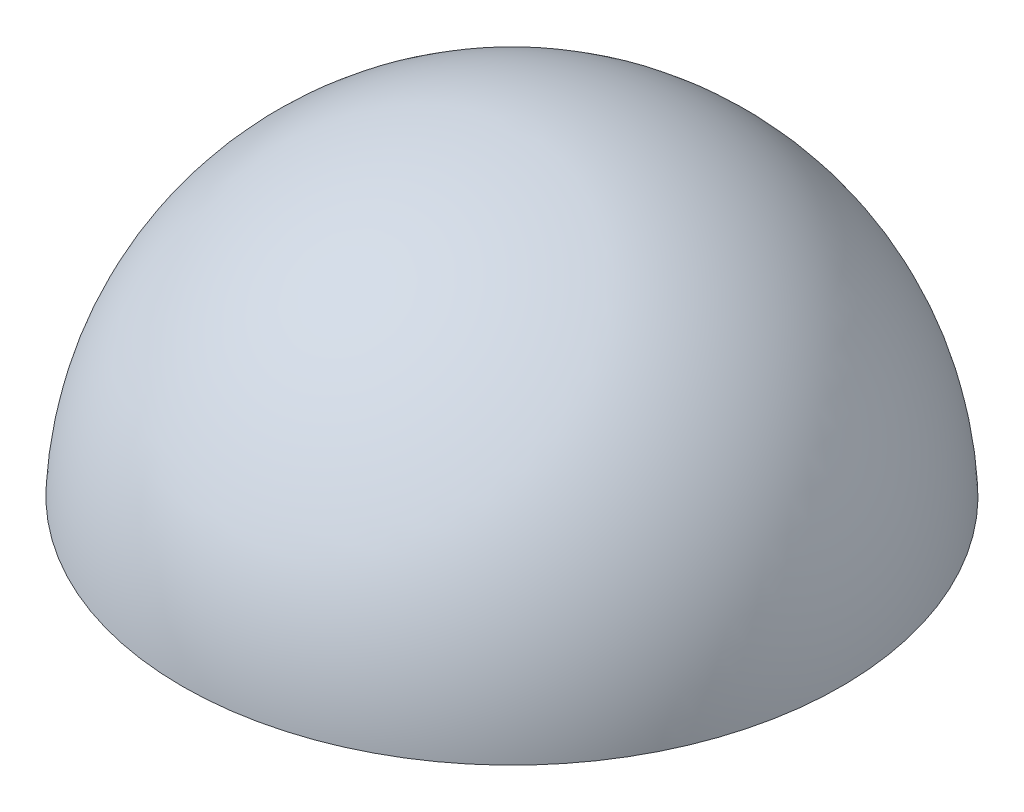
SolidWorks part; units mm, degrees
ref_plane "Front Plane" through (0, 0, 0) normal (0, 0, 1) x (1, 0, 0)
ref_plane "Top Plane" through (0, 0, 0) normal (0, 1, 0) x (1, 0, 0)
ref_plane "Right Plane" through (0, 0, 0) normal (1, 0, 0) x (0, 0, -1)
sketch "Sketch1" plane through (0, 0, 0) normal (0, 1, 0) x (1, 0, 0)
  line L0 (0, -44.45) -> (0, 44.45)
  arc A0 (0, 44.45) -> (0, -44.45) centre (0, 0) ccw
  arc A1 (0, 42.45) -> (0, -42.45) centre (0, 0) ccw
  circle A3 centre (0, 0) radius 44.45 construction
  circle A4 centre (0, 0) radius 42.45 construction
  point P1 (42.45, 0)
  point P6 (42.5077, 12.9959)
  dimension "D1" = 88.9
  dimension "D2" = 2
revolve "Revolve1" add sketch "Sketch1" angle 180 about L0 region at (-43.4561, 0, 0)
sketch "Sketch2" plane through (0, 0, 0) normal (0, 1, 0) x (1, 0, 0)
  circle A0 centre (0, 0) radius 44.45
extrude "Cut-Extrude1" cut sketch "Sketch2" along normal blind 2
sketch "30deg" plane through (0, 0, 0) normal (1, 0, 0) x (0, 0, -1)
  line L0 (0, 0) -> (38.4948, 22.225) construction
  line L1 (0, 0) -> (44.45, 0) construction
  line L7 (0, 0) -> (22.225, 38.4948) construction
  line L8 (0, 0) -> (44.45, 0) construction
  line L10 (0, 0) -> (38.4948, 22.225) construction
  line L25 (0, 0) -> (0, 49000) construction
  dimension "D2" = 3
  dimension "D3" = 30
  dimension "D1" = 44.45
sketch "Sketch4" plane through (0, 0, 0) normal (0, 1, 0) x (1, 0, 0)
  line L0 (0, 0) -> (0, 43.45)
  line L1 (0.5, 44.45) -> (-0.5, 44.45)
  line L2 (-0.5, 43.45) -> (0.5, 43.45)
  line L3 (-0.5, 43.45) -> (-0.5, 44.45)
  line L4 (0.5, 43.45) -> (0.5, 44.45)
  line L5 (0, 0) -> (21.725, 37.6288)
  line L6 (21.292, 37.8788) -> (21.792, 38.7448)
  line L7 (21.292, 37.8788) -> (22.158, 37.3788)
  line L8 (22.158, 37.3788) -> (22.658, 38.2448)
  line L9 (22.658, 38.2448) -> (21.792, 38.7448)
  line L10 (0, 0) -> (37.6288, 21.725)
  line L11 (37.3788, 22.158) -> (38.2448, 22.658)
  line L12 (37.3788, 22.158) -> (37.8788, 21.292)
  line L13 (37.8788, 21.292) -> (38.7448, 21.792)
  line L14 (38.7448, 21.792) -> (38.2448, 22.658)
  line L15 (0, 0) -> (43.45, 0)
  line L16 (43.45, 0.5) -> (44.45, 0.5)
  line L17 (43.45, 0.5) -> (43.45, -0.5)
  line L18 (43.45, -0.5) -> (44.45, -0.5)
  line L19 (44.45, -0.5) -> (44.45, 0.5)
  line L20 (0, 0) -> (37.6288, -21.725)
  line L21 (37.8788, -21.292) -> (38.7448, -21.792)
  line L22 (37.8788, -21.292) -> (37.3788, -22.158)
  line L23 (37.3788, -22.158) -> (38.2448, -22.658)
  line L24 (38.2448, -22.658) -> (38.7448, -21.792)
  line L25 (0, 0) -> (21.725, -37.6288)
  line L26 (22.158, -37.3788) -> (22.658, -38.2448)
  line L27 (22.158, -37.3788) -> (21.292, -37.8788)
  line L28 (21.292, -37.8788) -> (21.792, -38.7448)
  line L29 (21.792, -38.7448) -> (22.658, -38.2448)
  line L30 (0, 0) -> (0, -43.45)
  line L31 (0.5, -43.45) -> (0.5, -44.45)
  line L32 (0.5, -43.45) -> (-0.5, -43.45)
  line L33 (-0.5, -43.45) -> (-0.5, -44.45)
  line L34 (-0.5, -44.45) -> (0.5, -44.45)
  line L35 (0, 0) -> (-21.725, -37.6288)
  line L36 (-21.292, -37.8788) -> (-21.792, -38.7448)
  line L37 (-21.292, -37.8788) -> (-22.158, -37.3788)
  line L38 (-22.158, -37.3788) -> (-22.658, -38.2448)
  line L39 (-22.658, -38.2448) -> (-21.792, -38.7448)
  line L40 (0, 0) -> (-37.6288, -21.725)
  line L41 (-37.3788, -22.158) -> (-38.2448, -22.658)
  line L42 (-37.3788, -22.158) -> (-37.8788, -21.292)
  line L43 (-37.8788, -21.292) -> (-38.7448, -21.792)
  line L44 (-38.7448, -21.792) -> (-38.2448, -22.658)
  line L45 (0, 0) -> (-43.45, 0)
  line L46 (-43.45, -0.5) -> (-44.45, -0.5)
  line L47 (-43.45, -0.5) -> (-43.45, 0.5)
  line L48 (-43.45, 0.5) -> (-44.45, 0.5)
  line L49 (-44.45, 0.5) -> (-44.45, -0.5)
  line L50 (0, 0) -> (-37.6288, 21.725)
  line L51 (-37.8788, 21.292) -> (-38.7448, 21.792)
  line L52 (-37.8788, 21.292) -> (-37.3788, 22.158)
  line L53 (-37.3788, 22.158) -> (-38.2448, 22.658)
  line L54 (-38.2448, 22.658) -> (-38.7448, 21.792)
  line L55 (0, 0) -> (-21.725, 37.6288)
  line L56 (-22.158, 37.3788) -> (-22.658, 38.2448)
  line L57 (-22.158, 37.3788) -> (-21.292, 37.8788)
  line L58 (-21.292, 37.8788) -> (-21.792, 38.7448)
  line L59 (-21.792, 38.7448) -> (-22.658, 38.2448)
  line L60 (0, 0) -> (0, 43.45) construction
  line L61 (0, 0) -> (21.725, 37.6288) construction
  circle A0 centre (0, 0) radius 44.45 construction
  point P7 (0, 44.45)
  point P10 (0, 43.45)
  dimension "D1" = 88.9
  dimension "D2" = 1
  dimension "D3" = 1
  dimension "D5" = 30
  dimension "D4" = 12
ref_plane "Plane1" through (0, 44.45, 0) normal (0, 1, 0) x (1, 0, 0)
sketch "Sketch5" plane through (0, 44.45, 0) normal (0, 1, 0) x (1, 0, 0)
  circle A0 centre (0, 0) radius 0.5
  dimension "D1" = 1
sketch "Sketch6" plane through (0, 0, 0) normal (0, 0, 1) x (1, 0, 0)
  line L0 (44.45, 0) -> (-44.45, 0) construction
  line L1 (-43.45, 0) -> (-44.45, 0) construction
  arc A0 (-44.45, 0) -> (0, 44.45) centre (0, 0) cw
ref_axis "Axis1" through (0, 117.8347, 0) along (0, -1, 0)
sketch "Sketch7" plane through (0, 44.45, 0) normal (0, 1, 0) x (1, 0, 0)
  line L0 (0, 0) -> (0, 88.8986) construction
  line L4 (-0.5, 38.9916) -> (-0.5, 88.8986)
  line L5 (0.5, 38.9916) -> (0.5, 88.8986)
  line L7 (-0.5, 22.7195) -> (-0.5, 37.9915)
  line L9 (0.5, 22.7195) -> (0.5, 37.9915)
  line L10 (0, 0) -> (44.4493, 76.9884) construction
  line L11 (19.0628, 34.0177) -> (44.0163, 77.2384)
  line L12 (19.9288, 33.5177) -> (44.8823, 76.7384)
  line L13 (10.9267, 19.9257) -> (18.5628, 33.1516)
  line L14 (11.7928, 19.4257) -> (19.4288, 32.6516)
  line L17 (0, 0) -> (76.9884, 44.4493) construction
  line L18 (33.5177, 19.9288) -> (76.7384, 44.8823)
  line L19 (34.0177, 19.0628) -> (77.2384, 44.0163)
  line L20 (19.4257, 11.7928) -> (32.6516, 19.4288)
  line L21 (19.9257, 10.9267) -> (33.1516, 18.5628)
  line L24 (0, 0) -> (88.8986, 0) construction
  line L25 (38.9916, 0.5) -> (88.8986, 0.5)
  line L26 (38.9916, -0.5) -> (88.8986, -0.5)
  line L27 (22.7195, 0.5) -> (37.9915, 0.5)
  line L28 (22.7195, -0.5) -> (37.9915, -0.5)
  line L31 (0, 0) -> (76.9884, -44.4493) construction
  line L32 (34.0177, -19.0628) -> (77.2384, -44.0163)
  line L33 (33.5177, -19.9288) -> (76.7384, -44.8823)
  line L34 (19.9257, -10.9267) -> (33.1516, -18.5628)
  line L35 (19.4257, -11.7928) -> (32.6516, -19.4288)
  line L38 (0, 0) -> (44.4493, -76.9884) construction
  line L39 (19.9288, -33.5177) -> (44.8823, -76.7384)
  line L40 (19.0628, -34.0177) -> (44.0163, -77.2384)
  line L41 (11.7928, -19.4257) -> (19.4288, -32.6516)
  line L42 (10.9267, -19.9257) -> (18.5628, -33.1516)
  line L45 (0, 0) -> (0, -88.8986) construction
  line L46 (0.5, -38.9916) -> (0.5, -88.8986)
  line L47 (-0.5, -38.9916) -> (-0.5, -88.8986)
  line L48 (0.5, -22.7195) -> (0.5, -37.9915)
  line L49 (-0.5, -22.7195) -> (-0.5, -37.9915)
  line L52 (0, 0) -> (-44.4493, -76.9884) construction
  line L53 (-19.0628, -34.0177) -> (-44.0163, -77.2384)
  line L54 (-19.9288, -33.5177) -> (-44.8823, -76.7384)
  line L55 (-10.9267, -19.9257) -> (-18.5628, -33.1516)
  line L56 (-11.7928, -19.4257) -> (-19.4288, -32.6516)
  line L59 (0, 0) -> (-76.9884, -44.4493) construction
  line L60 (-33.5177, -19.9288) -> (-76.7384, -44.8823)
  line L61 (-34.0177, -19.0628) -> (-77.2384, -44.0163)
  line L62 (-19.4257, -11.7928) -> (-32.6516, -19.4288)
  line L63 (-19.9257, -10.9267) -> (-33.1516, -18.5628)
  line L66 (0, 0) -> (-88.8986, 0) construction
  line L67 (-38.9916, -0.5) -> (-88.8986, -0.5)
  line L68 (-38.9916, 0.5) -> (-88.8986, 0.5)
  line L69 (-22.7195, -0.5) -> (-37.9915, -0.5)
  line L70 (-22.7195, 0.5) -> (-37.9915, 0.5)
  line L73 (0, 0) -> (-76.9884, 44.4493) construction
  line L74 (-34.0177, 19.0628) -> (-77.2384, 44.0163)
  line L75 (-33.5177, 19.9288) -> (-76.7384, 44.8823)
  line L76 (-19.9257, 10.9267) -> (-33.1516, 18.5628)
  line L77 (-19.4257, 11.7928) -> (-32.6516, 19.4288)
  line L80 (0, 0) -> (-44.4493, 76.9884) construction
  line L81 (-19.9288, 33.5177) -> (-44.8823, 76.7384)
  line L82 (-19.0628, 34.0177) -> (-44.0163, 77.2384)
  line L83 (-11.7928, 19.4257) -> (-19.4288, 32.6516)
  line L84 (-10.9267, 19.9257) -> (-18.5628, 33.1516)
  line L87 (0, 0) -> (0.5, 0) construction
  line L89 (-0.5, 1.866) -> (-0.5, 21.7192)
  line L90 (-0.5, 1.866) -> (-10.4266, 19.0594)
  line L91 (0.5, 1.866) -> (10.4266, 19.0594)
  line L92 (0.5, 1.866) -> (0.5, 21.7192)
  line L93 (1.366, 1.366) -> (18.5594, 11.2926)
  line L94 (1.366, 1.366) -> (11.2926, 18.5594)
  line L95 (1.866, 0.5) -> (21.7192, 0.5)
  line L96 (1.866, 0.5) -> (19.0594, 10.4266)
  line L97 (1.866, -0.5) -> (19.0594, -10.4266)
  line L98 (1.866, -0.5) -> (21.7192, -0.5)
  line L99 (1.366, -1.366) -> (11.2926, -18.5594)
  line L100 (1.366, -1.366) -> (18.5594, -11.2926)
  line L101 (0.5, -1.866) -> (0.5, -21.7192)
  line L102 (0.5, -1.866) -> (10.4266, -19.0594)
  line L103 (-0.5, -1.866) -> (-10.4266, -19.0594)
  line L104 (-0.5, -1.866) -> (-0.5, -21.7192)
  line L105 (-1.366, -1.366) -> (-11.2926, -18.5594)
  line L106 (-1.366, -1.366) -> (-18.5594, -11.2926)
  line L107 (-1.866, -0.5) -> (-21.7192, -0.5)
  line L108 (-1.866, -0.5) -> (-19.0594, -10.4266)
  line L109 (-1.866, 0.5) -> (-19.0594, 10.4266)
  line L110 (-1.866, 0.5) -> (-21.7192, 0.5)
  line L111 (-1.366, 1.366) -> (-11.2926, 18.5594)
  line L112 (-1.366, 1.366) -> (-18.5594, 11.2926)
  circle A0 centre (0, 0) radius 22.225 construction
  circle A1 centre (0, 0) radius 38.4948 construction
  arc A2 (-0.5, 38.9916) -> (-19.0628, 34.0177) centre (0, 0) ccw
  arc A3 (-0.5, 22.7195) -> (-10.9267, 19.9257) centre (0, 0) ccw
  arc A4 (-0.5, 37.9915) -> (-18.5628, 33.1516) centre (0, 0) ccw
  arc A5 (-0.5, 21.7192) -> (-10.4266, 19.0594) centre (0, 0) ccw
  arc A6 (0.5, 88.8986) -> (-0.5, 88.8986) centre (0, 0) ccw
  circle A9 centre (0, 0) radius 88.9 construction
  circle A10 centre (0, 0) radius 38.9948 construction
  circle A11 centre (0, 0) radius 37.9948 construction
  circle A13 centre (0, 0) radius 21.725 construction
  circle A14 centre (0, 0) radius 22.725 construction
  arc A15 (44.8823, 76.7384) -> (44.0163, 77.2384) centre (0, 0) ccw
  arc A16 (77.2384, 44.0163) -> (76.7384, 44.8823) centre (0, 0) ccw
  arc A17 (88.8986, -0.5) -> (88.8986, 0.5) centre (0, 0) ccw
  arc A18 (76.7384, -44.8823) -> (77.2384, -44.0163) centre (0, 0) ccw
  arc A19 (44.0163, -77.2384) -> (44.8823, -76.7384) centre (0, 0) ccw
  arc A20 (-0.5, -88.8986) -> (0.5, -88.8986) centre (0, 0) ccw
  arc A21 (-44.8823, -76.7384) -> (-44.0163, -77.2384) centre (0, 0) ccw
  arc A22 (-77.2384, -44.0163) -> (-76.7384, -44.8823) centre (0, 0) ccw
  arc A23 (-88.8986, 0.5) -> (-88.8986, -0.5) centre (0, 0) ccw
  arc A24 (-76.7384, 44.8823) -> (-77.2384, 44.0163) centre (0, 0) ccw
  arc A25 (-44.0163, 77.2384) -> (-44.8823, 76.7384) centre (0, 0) ccw
  arc A26 (-34.0177, 19.0628) -> (-38.9916, 0.5) centre (0, 0) ccw
  arc A27 (-33.1516, 18.5628) -> (-37.9915, 0.5) centre (0, 0) ccw
  arc A28 (-19.9288, 33.5177) -> (-33.5177, 19.9288) centre (0, 0) ccw
  arc A29 (-19.4288, 32.6516) -> (-32.6516, 19.4288) centre (0, 0) ccw
  arc A30 (19.0628, 34.0177) -> (0.5, 38.9916) centre (0, 0) ccw
  arc A31 (18.5628, 33.1516) -> (0.5, 37.9915) centre (0, 0) ccw
  arc A32 (32.6516, 19.4288) -> (19.4288, 32.6516) centre (0, 0) ccw
  arc A33 (33.5177, 19.9288) -> (19.9288, 33.5177) centre (0, 0) ccw
  arc A34 (37.9915, 0.5) -> (33.1516, 18.5628) centre (0, 0) ccw
  arc A35 (38.9916, 0.5) -> (34.0177, 19.0628) centre (0, 0) ccw
  arc A36 (33.1516, -18.5628) -> (37.9915, -0.5) centre (0, 0) ccw
  arc A37 (34.0177, -19.0628) -> (38.9916, -0.5) centre (0, 0) ccw
  arc A38 (19.4288, -32.6516) -> (32.6516, -19.4288) centre (0, 0) ccw
  arc A39 (19.9288, -33.5177) -> (33.5177, -19.9288) centre (0, 0) ccw
  arc A40 (0.5, -37.9915) -> (18.5628, -33.1516) centre (0, 0) ccw
  arc A41 (0.5, -38.9916) -> (19.0628, -34.0177) centre (0, 0) ccw
  arc A42 (-18.5628, -33.1516) -> (-0.5, -37.9915) centre (0, 0) ccw
  arc A43 (-19.0628, -34.0177) -> (-0.5, -38.9916) centre (0, 0) ccw
  arc A44 (-33.5177, -19.9288) -> (-19.9288, -33.5177) centre (0, 0) ccw
  arc A45 (-32.6516, -19.4288) -> (-19.4288, -32.6516) centre (0, 0) ccw
  arc A46 (-38.9916, -0.5) -> (-34.0177, -19.0628) centre (0, 0) ccw
  arc A47 (-37.9915, -0.5) -> (-33.1516, -18.5628) centre (0, 0) ccw
  arc A48 (-11.7928, 19.4257) -> (-19.4257, 11.7928) centre (0, 0) ccw
  arc A49 (-11.2926, 18.5594) -> (-18.5594, 11.2926) centre (0, 0) ccw
  arc A50 (-19.9257, 10.9267) -> (-22.7195, 0.5) centre (0, 0) ccw
  arc A51 (-19.0594, 10.4266) -> (-21.7192, 0.5) centre (0, 0) ccw
  arc A52 (-21.7192, -0.5) -> (-19.0594, -10.4266) centre (0, 0) ccw
  arc A53 (-22.7195, -0.5) -> (-19.9257, -10.9267) centre (0, 0) ccw
  arc A54 (10.4266, 19.0594) -> (0.5, 21.7192) centre (0, 0) ccw
  arc A55 (10.9267, 19.9257) -> (0.5, 22.7195) centre (0, 0) ccw
  arc A56 (18.5594, 11.2926) -> (11.2926, 18.5594) centre (0, 0) ccw
  arc A57 (19.4257, 11.7928) -> (11.7928, 19.4257) centre (0, 0) ccw
  arc A58 (21.7192, 0.5) -> (19.0594, 10.4266) centre (0, 0) ccw
  arc A59 (22.7195, 0.5) -> (19.9257, 10.9267) centre (0, 0) ccw
  arc A60 (19.9257, -10.9267) -> (22.7195, -0.5) centre (0, 0) ccw
  arc A61 (19.0594, -10.4266) -> (21.7192, -0.5) centre (0, 0) ccw
  arc A62 (11.2926, -18.5594) -> (18.5594, -11.2926) centre (0, 0) ccw
  arc A63 (11.7928, -19.4257) -> (19.4257, -11.7928) centre (0, 0) ccw
  arc A64 (0.5, -22.7195) -> (10.9267, -19.9257) centre (0, 0) ccw
  arc A65 (0.5, -21.7192) -> (10.4266, -19.0594) centre (0, 0) ccw
  arc A66 (-10.4266, -19.0594) -> (-0.5, -21.7192) centre (0, 0) ccw
  arc A67 (-10.9267, -19.9257) -> (-0.5, -22.7195) centre (0, 0) ccw
  arc A68 (-19.4257, -11.7928) -> (-11.7928, -19.4257) centre (0, 0) ccw
  arc A69 (-18.5594, -11.2926) -> (-11.2926, -18.5594) centre (0, 0) ccw
  point P11 (21.725, 0)
  point P13 (22.725, 0)
  point P17 (0.5, 0)
  point P19 (-0.5, 0)
  point P27 (38.9948, 0)
  point P30 (37.9948, 0)
  point P114 (-1.366, 1.366)
  dimension "D5" = 177.8
  dimension "D1" = 0.5
  dimension "D2" = 0.5
  dimension "D6" = 12
sketch "Sketch9" plane through (0, 44.45, 0) normal (0, 1, 0) x (1, 0, 0)
  line L0 (0, 0) -> (0, -88.9)
  circle A0 centre (0, 0) radius 22.225
  circle A1 centre (0, 0) radius 38.4948
  circle A2 centre (0, 0) radius 88.9
  circle A3 centre (0, 0) radius 38.4948 construction
  circle A4 centre (0, 0) radius 22.225 construction
  dimension "D1" = 177.8
sketch "Sketch10" plane through (0, 44.45, 0) normal (0, 1, 0) x (1, 0, 0)
  line L0 (88.9, 0) -> (-88.9, 0) construction
  line L1 (0, 88.9) -> (0, -88.9) construction
  line L2 (-29.64, 88.9) -> (-29.64, -88.9) construction
  line L3 (-59.28, 88.9) -> (-59.28, -88.9) construction
  line L4 (-88.92, 88.9) -> (-88.92, -88.9) construction
  line L5 (29.64, 88.9) -> (29.64, -88.9) construction
  line L6 (59.28, 88.9) -> (59.28, -88.9) construction
  line L7 (88.92, 88.9) -> (88.92, -88.9) construction
  line L8 (-89.42, 88.9) -> (-89.42, -88.9)
  line L9 (-59.78, 88.9) -> (-59.78, 0.5)
  line L10 (-30.14, 88.9) -> (-30.14, 0.5)
  line L11 (-0.5, 88.9) -> (-0.5, 0.5)
  line L12 (29.14, 88.9) -> (29.14, 0.5)
  line L13 (58.78, 88.9) -> (58.78, 0.5)
  line L14 (88.42, 88.9) -> (88.42, 0.5)
  line L15 (-88.42, 88.9) -> (-88.42, 0.5)
  line L16 (-58.78, 88.9) -> (-58.78, 0.5)
  line L17 (-29.14, 88.9) -> (-29.14, 0.5)
  line L18 (0.5, 88.9) -> (0.5, 0.5)
  line L19 (30.14, 88.9) -> (30.14, 0.5)
  line L20 (59.78, 88.9) -> (59.78, 0.5)
  line L21 (89.42, 88.9) -> (89.42, -88.9)
  line L22 (88.42, 0.5) -> (59.78, 0.5)
  line L23 (88.42, -0.5) -> (59.78, -0.5)
  line L24 (-88.42, -0.5) -> (-88.42, -88.9)
  line L25 (88.9, 0.5) -> (-88.9, 0.5) construction
  line L26 (88.9, -0.5) -> (-88.9, -0.5) construction
  line L27 (-59.78, 0.5) -> (-88.42, 0.5)
  line L28 (-88.42, 88.9) -> (-88.42, -88.9) construction
  line L29 (-59.78, -0.5) -> (-88.42, -0.5)
  line L30 (-59.78, -0.5) -> (-59.78, -88.9)
  line L31 (-58.78, -0.5) -> (-58.78, -88.9)
  line L32 (-59.78, 88.9) -> (-59.78, -88.9) construction
  line L33 (-30.14, -0.5) -> (-30.14, -88.9)
  line L34 (-58.78, 88.9) -> (-58.78, -88.9) construction
  line L35 (-30.14, 88.9) -> (-30.14, -88.9) construction
  line L36 (-29.14, -0.5) -> (-29.14, -88.9)
  line L37 (-29.14, 88.9) -> (-29.14, -88.9) construction
  line L38 (-0.5, -0.5) -> (-0.5, -88.9)
  line L39 (-0.5, 88.9) -> (-0.5, -88.9) construction
  line L40 (0.5, -0.5) -> (0.5, -88.9)
  line L41 (0.5, 88.9) -> (0.5, -88.9) construction
  line L42 (29.14, -0.5) -> (29.14, -88.9)
  line L43 (29.14, 88.9) -> (29.14, -88.9) construction
  line L44 (30.14, -0.5) -> (30.14, -88.9)
  line L45 (30.14, 88.9) -> (30.14, -88.9) construction
  line L46 (58.78, -0.5) -> (58.78, -88.9)
  line L47 (58.78, 88.9) -> (58.78, -88.9) construction
  line L48 (59.78, -0.5) -> (59.78, -88.9)
  line L49 (59.78, 88.9) -> (59.78, -88.9) construction
  line L50 (88.42, -0.5) -> (88.42, -88.9)
  line L51 (88.42, 88.9) -> (88.42, -88.9) construction
  line L52 (58.78, 0.5) -> (30.14, 0.5)
  line L53 (58.78, -0.5) -> (30.14, -0.5)
  line L54 (-30.14, 0.5) -> (-58.78, 0.5)
  line L55 (-30.14, -0.5) -> (-58.78, -0.5)
  line L56 (-0.5, 0.5) -> (-29.14, 0.5)
  line L57 (-0.5, -0.5) -> (-29.14, -0.5)
  line L58 (29.14, 0.5) -> (0.5, 0.5)
  line L59 (29.14, -0.5) -> (0.5, -0.5)
  arc A0 (-89.42, 88.9) -> (-88.42, 88.9) centre (-88.92, 88.9) cw
  arc A1 (-89.42, -88.9) -> (-88.42, -88.9) centre (-88.92, -88.9) ccw
  arc A2 (-59.78, 88.9) -> (-58.78, 88.9) centre (-59.28, 88.9) cw
  arc A3 (-59.78, -88.9) -> (-58.78, -88.9) centre (-59.28, -88.9) ccw
  arc A4 (-30.14, 88.9) -> (-29.14, 88.9) centre (-29.64, 88.9) cw
  arc A5 (-30.14, -88.9) -> (-29.14, -88.9) centre (-29.64, -88.9) ccw
  arc A6 (-0.5, 88.9) -> (0.5, 88.9) centre (0, 88.9) cw
  arc A7 (-0.5, -88.9) -> (0.5, -88.9) centre (0, -88.9) ccw
  arc A8 (29.14, 88.9) -> (30.14, 88.9) centre (29.64, 88.9) cw
  arc A9 (29.14, -88.9) -> (30.14, -88.9) centre (29.64, -88.9) ccw
  arc A10 (58.78, 88.9) -> (59.78, 88.9) centre (59.28, 88.9) cw
  arc A11 (58.78, -88.9) -> (59.78, -88.9) centre (59.28, -88.9) ccw
  arc A12 (88.42, 88.9) -> (89.42, 88.9) centre (88.92, 88.9) cw
  arc A13 (88.42, -88.9) -> (89.42, -88.9) centre (88.92, -88.9) ccw
  arc A15 (-88.9, 0.5) -> (-88.92, 0.4996) centre (-88.9, 0) ccw
  arc A16 (-88.92, -0.4996) -> (-88.9, -0.5) centre (-88.9, 0) ccw
  point P4 (0, 0)
  point P8 (0, 0)
  dimension "D1" = 177.8
  dimension "D3" = 0.5
  dimension "D4" = 0.5
  dimension "D5" = 0.5
  dimension "D6" = 0.5
  dimension "D2" = 4
sketch "Sketch13" plane through (0, 44.45, 0) normal (0, 1, 0) x (1, 0, 0)
  line L0 (0, -11.5265) -> (0, 11.5265) construction
  line L1 (-11.5265, 0) -> (11.5265, 0) construction
  line L2 (-11.5265, -0.5) -> (-0.5, -0.5)
  line L3 (-18.1069, 3.2902) -> (-11.5265, 3.2902) construction
  line L4 (-18.1069, 3.2902) -> (-18.1069, -3.2902) construction
  line L5 (-18.1069, -3.2902) -> (-11.5265, -3.2902) construction
  line L6 (-11.5265, 3.2902) -> (-11.5265, -3.2902) construction
  line L7 (-3.2902, 18.1069) -> (3.2902, 18.1069) construction
  line L8 (-3.2902, 18.1069) -> (-3.2902, 11.5265) construction
  line L9 (-3.2902, 11.5265) -> (3.2902, 11.5265) construction
  line L10 (3.2902, 18.1069) -> (3.2902, 11.5265) construction
  line L11 (0.5, -11.5265) -> (0.5, -0.5)
  line L12 (-11.5265, 0.5) -> (-0.5, 0.5)
  line L13 (-0.5, -11.5265) -> (-0.5, -0.5)
  line L14 (-0.5, 0.5) -> (-0.5, 11.5265)
  line L15 (0.5, 0.5) -> (0.5, 11.5265)
  line L16 (-0.5, -11.5265) -> (-0.5, 11.5265) construction
  line L17 (0.5, 0.5) -> (11.5265, 0.5)
  line L18 (0.5, -11.5265) -> (0.5, 11.5265) construction
  line L19 (0.5, -0.5) -> (11.5265, -0.5)
  line L20 (-11.5265, 0.5) -> (11.5265, 0.5) construction
  line L21 (-11.5265, 0.5) -> (-11.5265, -0.5)
  line L22 (-11.5265, -0.5) -> (11.5265, -0.5) construction
  line L23 (11.5265, 0.5) -> (11.5265, -0.5)
  line L24 (-0.5, -11.5265) -> (0.5, -11.5265)
  line L25 (-0.5, 11.5265) -> (0.5, 11.5265)
  line L26 (18.1035, -0.5) -> (29.13, -0.5)
  line L27 (30.13, -11.5265) -> (30.13, -0.5)
  line L28 (18.1035, 0.5) -> (29.13, 0.5)
  line L29 (29.13, -11.5265) -> (29.13, -0.5)
  line L30 (29.13, 0.5) -> (29.13, 11.5265)
  line L31 (30.13, 0.5) -> (30.13, 11.5265)
  line L32 (30.13, 0.5) -> (41.1565, 0.5)
  line L33 (30.13, -0.5) -> (41.1565, -0.5)
  line L34 (18.1035, 0.5) -> (18.1035, -0.5)
  line L35 (41.1565, 0.5) -> (41.1565, -0.5)
  line L36 (29.13, -11.5265) -> (30.13, -11.5265)
  line L37 (29.13, 11.5265) -> (30.13, 11.5265)
  line L38 (29.63, -11.5265) -> (29.63, 11.5265) construction
  line L39 (18.1035, 0) -> (41.1565, 0) construction
  line L40 (11.5231, 3.2902) -> (18.1035, 3.2902) construction
  line L41 (11.5231, 3.2902) -> (11.5231, -3.2902) construction
  line L42 (11.5231, -3.2902) -> (18.1035, -3.2902) construction
  line L43 (18.1035, 3.2902) -> (18.1035, -3.2902) construction
  line L44 (26.3398, 18.1069) -> (32.9202, 18.1069) construction
  line L45 (26.3398, 18.1069) -> (26.3398, 11.5265) construction
  line L46 (26.3398, 11.5265) -> (32.9202, 11.5265) construction
  line L47 (32.9202, 18.1069) -> (32.9202, 11.5265) construction
  line L48 (47.7335, -0.5) -> (58.76, -0.5)
  line L49 (59.76, -11.5265) -> (59.76, -0.5)
  line L50 (47.7335, 0.5) -> (58.76, 0.5)
  line L51 (58.76, -11.5265) -> (58.76, -0.5)
  line L52 (58.76, 0.5) -> (58.76, 11.5265)
  line L53 (59.76, 0.5) -> (59.76, 11.5265)
  line L54 (59.76, 0.5) -> (70.7865, 0.5)
  line L55 (59.76, -0.5) -> (70.7865, -0.5)
  line L56 (47.7335, 0.5) -> (47.7335, -0.5)
  line L57 (70.7865, 0.5) -> (70.7865, -0.5)
  line L58 (58.76, -11.5265) -> (59.76, -11.5265)
  line L59 (58.76, 11.5265) -> (59.76, 11.5265)
  line L60 (59.26, -11.5265) -> (59.26, 11.5265) construction
  line L61 (47.7335, 0) -> (70.7865, 0) construction
  line L62 (41.1531, 3.2902) -> (47.7335, 3.2902) construction
  line L63 (41.1531, 3.2902) -> (41.1531, -3.2902) construction
  line L64 (41.1531, -3.2902) -> (47.7335, -3.2902) construction
  line L65 (47.7335, 3.2902) -> (47.7335, -3.2902) construction
  line L66 (55.9698, 18.1069) -> (62.5502, 18.1069) construction
  line L67 (55.9698, 18.1069) -> (55.9698, 11.5265) construction
  line L68 (55.9698, 11.5265) -> (62.5502, 11.5265) construction
  line L69 (62.5502, 18.1069) -> (62.5502, 11.5265) construction
  line L70 (-11.5265, 29.13) -> (-0.5, 29.13)
  line L71 (0.5, 18.1035) -> (0.5, 29.13)
  line L72 (-11.5265, 30.13) -> (-0.5, 30.13)
  line L73 (-0.5, 18.1035) -> (-0.5, 29.13)
  line L74 (-0.5, 30.13) -> (-0.5, 41.1565)
  line L75 (0.5, 30.13) -> (0.5, 41.1565)
  line L76 (0.5, 30.13) -> (11.5265, 30.13)
  line L77 (0.5, 29.13) -> (11.5265, 29.13)
  line L78 (-11.5265, 30.13) -> (-11.5265, 29.13)
  line L79 (11.5265, 30.13) -> (11.5265, 29.13)
  line L80 (-0.5, 18.1035) -> (0.5, 18.1035)
  line L81 (-0.5, 41.1565) -> (0.5, 41.1565)
  line L82 (18.1035, 29.13) -> (29.13, 29.13)
  line L83 (30.13, 18.1035) -> (30.13, 29.13)
  line L84 (18.1035, 30.13) -> (29.13, 30.13)
  line L85 (29.13, 18.1035) -> (29.13, 29.13)
  line L86 (29.13, 30.13) -> (29.13, 41.1565)
  line L87 (30.13, 30.13) -> (30.13, 41.1565)
  line L88 (30.13, 30.13) -> (41.1565, 30.13)
  line L89 (30.13, 29.13) -> (41.1565, 29.13)
  line L90 (18.1035, 30.13) -> (18.1035, 29.13)
  line L91 (41.1565, 30.13) -> (41.1565, 29.13)
  line L92 (29.13, 18.1035) -> (30.13, 18.1035)
  line L93 (29.13, 41.1565) -> (30.13, 41.1565)
  line L94 (47.7335, 29.13) -> (58.76, 29.13)
  line L95 (59.76, 18.1035) -> (59.76, 29.13)
  line L96 (47.7335, 30.13) -> (58.76, 30.13)
  line L97 (58.76, 18.1035) -> (58.76, 29.13)
  line L98 (58.76, 30.13) -> (58.76, 41.1565)
  line L99 (59.76, 30.13) -> (59.76, 41.1565)
  line L100 (59.76, 30.13) -> (70.7865, 30.13)
  line L101 (59.76, 29.13) -> (70.7865, 29.13)
  line L102 (47.7335, 30.13) -> (47.7335, 29.13)
  line L103 (70.7865, 30.13) -> (70.7865, 29.13)
  line L104 (58.76, 18.1035) -> (59.76, 18.1035)
  line L105 (58.76, 41.1565) -> (59.76, 41.1565)
  line L106 (0, 18.1035) -> (0, 41.1565) construction
  line L107 (-11.5265, 29.63) -> (11.5265, 29.63) construction
  line L108 (-18.1069, 32.9202) -> (-11.5265, 32.9202) construction
  line L109 (-18.1069, 32.9202) -> (-18.1069, 26.3398) construction
  line L110 (-18.1069, 26.3398) -> (-11.5265, 26.3398) construction
  line L111 (-11.5265, 32.9202) -> (-11.5265, 26.3398) construction
  line L112 (-3.2902, 47.7369) -> (3.2902, 47.7369) construction
  line L113 (-3.2902, 47.7369) -> (-3.2902, 41.1565) construction
  line L114 (-3.2902, 41.1565) -> (3.2902, 41.1565) construction
  line L115 (3.2902, 47.7369) -> (3.2902, 41.1565) construction
  line L116 (29.63, 18.1035) -> (29.63, 41.1565) construction
  line L117 (18.1035, 29.63) -> (41.1565, 29.63) construction
  line L118 (11.5231, 32.9202) -> (18.1035, 32.9202) construction
  line L119 (11.5231, 32.9202) -> (11.5231, 26.3398) construction
  line L120 (11.5231, 26.3398) -> (18.1035, 26.3398) construction
  line L121 (18.1035, 32.9202) -> (18.1035, 26.3398) construction
  line L122 (26.3398, 47.7369) -> (32.9202, 47.7369) construction
  line L123 (26.3398, 47.7369) -> (26.3398, 41.1565) construction
  line L124 (26.3398, 41.1565) -> (32.9202, 41.1565) construction
  line L125 (32.9202, 47.7369) -> (32.9202, 41.1565) construction
  line L126 (59.26, 18.1035) -> (59.26, 41.1565) construction
  line L127 (47.7335, 29.63) -> (70.7865, 29.63) construction
  line L128 (41.1531, 32.9202) -> (47.7335, 32.9202) construction
  line L129 (41.1531, 32.9202) -> (41.1531, 26.3398) construction
  line L130 (41.1531, 26.3398) -> (47.7335, 26.3398) construction
  line L131 (47.7335, 32.9202) -> (47.7335, 26.3398) construction
  line L132 (55.9698, 47.7369) -> (62.5502, 47.7369) construction
  line L133 (55.9698, 47.7369) -> (55.9698, 41.1565) construction
  line L134 (55.9698, 41.1565) -> (62.5502, 41.1565) construction
  line L135 (62.5502, 47.7369) -> (62.5502, 41.1565) construction
  line L136 (-11.5265, 58.76) -> (-0.5, 58.76)
  line L137 (0.5, 47.7335) -> (0.5, 58.76)
  line L138 (-11.5265, 59.76) -> (-0.5, 59.76)
  line L139 (-0.5, 47.7335) -> (-0.5, 58.76)
  line L140 (-0.5, 59.76) -> (-0.5, 70.7865)
  line L141 (0.5, 59.76) -> (0.5, 70.7865)
  line L142 (0.5, 59.76) -> (11.5265, 59.76)
  line L143 (0.5, 58.76) -> (11.5265, 58.76)
  line L144 (-11.5265, 59.76) -> (-11.5265, 58.76)
  line L145 (11.5265, 59.76) -> (11.5265, 58.76)
  line L146 (-0.5, 47.7335) -> (0.5, 47.7335)
  line L147 (-0.5, 70.7865) -> (0.5, 70.7865)
  line L148 (18.1035, 58.76) -> (29.13, 58.76)
  line L149 (30.13, 47.7335) -> (30.13, 58.76)
  line L150 (18.1035, 59.76) -> (29.13, 59.76)
  line L151 (29.13, 47.7335) -> (29.13, 58.76)
  line L152 (29.13, 59.76) -> (29.13, 70.7865)
  line L153 (30.13, 59.76) -> (30.13, 70.7865)
  line L154 (30.13, 59.76) -> (41.1565, 59.76)
  line L155 (30.13, 58.76) -> (41.1565, 58.76)
  line L156 (18.1035, 59.76) -> (18.1035, 58.76)
  line L157 (41.1565, 59.76) -> (41.1565, 58.76)
  line L158 (29.13, 47.7335) -> (30.13, 47.7335)
  line L159 (29.13, 70.7865) -> (30.13, 70.7865)
  line L160 (47.7335, 58.76) -> (58.76, 58.76)
  line L161 (59.76, 47.7335) -> (59.76, 58.76)
  line L162 (47.7335, 59.76) -> (58.76, 59.76)
  line L163 (58.76, 47.7335) -> (58.76, 58.76)
  line L164 (58.76, 59.76) -> (58.76, 70.7865)
  line L165 (59.76, 59.76) -> (59.76, 70.7865)
  line L166 (59.76, 59.76) -> (70.7865, 59.76)
  line L167 (59.76, 58.76) -> (70.7865, 58.76)
  line L168 (47.7335, 59.76) -> (47.7335, 58.76)
  line L169 (70.7865, 59.76) -> (70.7865, 58.76)
  line L170 (58.76, 47.7335) -> (59.76, 47.7335)
  line L171 (58.76, 70.7865) -> (59.76, 70.7865)
  line L172 (0, 47.7335) -> (0, 70.7865) construction
  line L173 (-11.5265, 59.26) -> (11.5265, 59.26) construction
  line L174 (-18.1069, 62.5502) -> (-11.5265, 62.5502) construction
  line L175 (-18.1069, 62.5502) -> (-18.1069, 55.9698) construction
  line L176 (-18.1069, 55.9698) -> (-11.5265, 55.9698) construction
  line L177 (-11.5265, 62.5502) -> (-11.5265, 55.9698) construction
  line L178 (-3.2902, 77.3669) -> (3.2902, 77.3669) construction
  line L179 (-3.2902, 77.3669) -> (-3.2902, 70.7865) construction
  line L180 (-3.2902, 70.7865) -> (3.2902, 70.7865) construction
  line L181 (3.2902, 77.3669) -> (3.2902, 70.7865) construction
  line L182 (29.63, 47.7335) -> (29.63, 70.7865) construction
  line L183 (18.1035, 59.26) -> (41.1565, 59.26) construction
  line L184 (11.5231, 62.5502) -> (18.1035, 62.5502) construction
  line L185 (11.5231, 62.5502) -> (11.5231, 55.9698) construction
  line L186 (11.5231, 55.9698) -> (18.1035, 55.9698) construction
  line L187 (18.1035, 62.5502) -> (18.1035, 55.9698) construction
  line L188 (26.3398, 77.3669) -> (32.9202, 77.3669) construction
  line L189 (26.3398, 77.3669) -> (26.3398, 70.7865) construction
  line L190 (26.3398, 70.7865) -> (32.9202, 70.7865) construction
  line L191 (32.9202, 77.3669) -> (32.9202, 70.7865) construction
  line L192 (59.26, 47.7335) -> (59.26, 70.7865) construction
  line L193 (47.7335, 59.26) -> (70.7865, 59.26) construction
  line L194 (41.1531, 62.5502) -> (47.7335, 62.5502) construction
  line L195 (41.1531, 62.5502) -> (41.1531, 55.9698) construction
  line L196 (41.1531, 55.9698) -> (47.7335, 55.9698) construction
  line L197 (47.7335, 62.5502) -> (47.7335, 55.9698) construction
  line L198 (55.9698, 77.3669) -> (62.5502, 77.3669) construction
  line L199 (55.9698, 77.3669) -> (55.9698, 70.7865) construction
  line L200 (55.9698, 70.7865) -> (62.5502, 70.7865) construction
  line L201 (62.5502, 77.3669) -> (62.5502, 70.7865) construction
  circle A0 centre (0, 0) radius 88.9 construction
  point P4 (0, 0)
  point P8 (0, 0)
  point P12 (-11.5265, 0)
  point P35 (29.63, 0)
  point P38 (29.63, 0)
  point P61 (59.26, 0)
  point P64 (59.26, 0)
  point P86 (0, 29.63)
  point P89 (0, 29.63)
  point P112 (29.63, 29.63)
  point P115 (29.63, 29.63)
  point P138 (59.26, 29.63)
  point P141 (59.26, 29.63)
  point P164 (0, 59.26)
  point P167 (0, 59.26)
  point P190 (29.63, 59.26)
  point P193 (29.63, 59.26)
  point P216 (59.26, 59.26)
  point P219 (59.26, 59.26)
  dimension "D1" = 177.8
  dimension "D2" = 29.6333
  dimension "D3" = 0.5
  dimension "D4" = 0.5
  dimension "D5" = 3
  dimension "D6" = 3
sketch "Sketch14" plane through (0, 44.45, 0) normal (0, 1, 0) x (1, 0, 0)
  line L0 (0, -40.6334) -> (0, -48.2866) construction
  line L13 (3.8266, -44.46) -> (-3.8266, -44.46) construction
  line L14 (3.8266, -43.96) -> (0.5, -43.96)
  line L15 (-10.99, -46.1691) -> (-3.8266, -46.1691) construction
  line L16 (-10.99, -46.1691) -> (-10.99, -42.7509) construction
  line L17 (-10.99, -42.7509) -> (-3.8266, -42.7509) construction
  line L18 (-3.8266, -46.1691) -> (-3.8266, -42.7509) construction
  line L19 (3.8266, -29.14) -> (0.5, -29.14)
  line L20 (-0.5, -25.8134) -> (-0.5, -29.14)
  line L21 (-3.5817, -37.1771) -> (3.5817, -37.1771) construction
  line L22 (-3.5817, -37.1771) -> (-3.5817, -39.47) construction
  line L23 (-3.5817, -39.47) -> (3.5817, -39.47) construction
  line L24 (3.5817, -37.1771) -> (3.5817, -39.47) construction
  line L25 (3.8266, -30.14) -> (0.5, -30.14)
  line L26 (0.5, -25.8134) -> (0.5, -29.14)
  line L27 (-0.5, -40.6334) -> (-0.5, -43.96)
  line L28 (3.8266, -44.96) -> (0.5, -44.96)
  line L29 (0.5, -40.6334) -> (0.5, -43.96)
  line L30 (3.8266, -43.96) -> (3.8266, -44.96)
  line L31 (-3.8266, -43.96) -> (-3.8266, -44.96)
  line L32 (-0.5, -40.6334) -> (0.5, -40.6334)
  line L33 (-0.5, -48.2866) -> (0.5, -48.2866)
  line L34 (-0.5, -44.96) -> (-0.5, -48.2866)
  line L35 (-0.5, -44.96) -> (-3.8266, -44.96)
  line L36 (-0.5, -40.6334) -> (-0.5, -48.2866) construction
  line L37 (0.5, -44.96) -> (0.5, -48.2866)
  line L38 (3.8266, -44.96) -> (-3.8266, -44.96) construction
  line L39 (-0.5, -43.96) -> (-3.8266, -43.96)
  line L40 (0.5, -40.6334) -> (0.5, -48.2866) construction
  line L41 (3.8266, -29.14) -> (3.8266, -30.14)
  line L42 (3.8266, -43.96) -> (-3.8266, -43.96) construction
  line L43 (-3.8266, -29.14) -> (-3.8266, -30.14)
  line L44 (-0.5, -25.8134) -> (0.5, -25.8134)
  line L45 (-0.5, -33.4666) -> (0.5, -33.4666)
  line L46 (-0.5, -30.14) -> (-0.5, -33.4666)
  line L47 (-0.5, -30.14) -> (-3.8266, -30.14)
  line L48 (0.5, -30.14) -> (0.5, -33.4666)
  line L49 (-0.5, -29.14) -> (-3.8266, -29.14)
  line L50 (0, -25.8134) -> (0, -33.4666) construction
  line L51 (3.8266, -29.64) -> (-3.8266, -29.64) construction
  line L52 (-10.99, -31.3491) -> (-3.8266, -31.3491) construction
  line L53 (-10.99, -31.3491) -> (-10.99, -27.9309) construction
  line L54 (-10.99, -27.9309) -> (-3.8266, -27.9309) construction
  line L55 (-3.8266, -31.3491) -> (-3.8266, -27.9309) construction
  line L56 (-3.5817, -22.3571) -> (3.5817, -22.3571) construction
  line L57 (-3.5817, -22.3571) -> (-3.5817, -24.65) construction
  line L58 (-3.5817, -24.65) -> (3.5817, -24.65) construction
  line L59 (3.5817, -22.3571) -> (3.5817, -24.65) construction
  line L60 (3.8266, -14.32) -> (0.5, -14.32)
  line L61 (-0.5, -10.9934) -> (-0.5, -14.32)
  line L62 (3.8266, -15.32) -> (0.5, -15.32)
  line L63 (0.5, -10.9934) -> (0.5, -14.32)
  line L64 (3.8266, -14.32) -> (3.8266, -15.32)
  line L65 (-3.8266, -14.32) -> (-3.8266, -15.32)
  line L66 (-0.5, -10.9934) -> (0.5, -10.9934)
  line L67 (-0.5, -18.6466) -> (0.5, -18.6466)
  line L68 (-0.5, -15.32) -> (-0.5, -18.6466)
  line L69 (-0.5, -15.32) -> (-3.8266, -15.32)
  line L70 (0.5, -15.32) -> (0.5, -18.6466)
  line L71 (-0.5, -14.32) -> (-3.8266, -14.32)
  line L72 (0, -10.9934) -> (0, -18.6466) construction
  line L73 (3.8266, -14.82) -> (-3.8266, -14.82) construction
  line L74 (-10.99, -16.5291) -> (-3.8266, -16.5291) construction
  line L75 (-10.99, -16.5291) -> (-10.99, -13.1109) construction
  line L76 (-10.99, -13.1109) -> (-3.8266, -13.1109) construction
  line L77 (-3.8266, -16.5291) -> (-3.8266, -13.1109) construction
  line L78 (-3.5817, -7.5371) -> (3.5817, -7.5371) construction
  line L79 (-3.5817, -7.5371) -> (-3.5817, -9.83) construction
  line L80 (-3.5817, -9.83) -> (3.5817, -9.83) construction
  line L81 (3.5817, -7.5371) -> (3.5817, -9.83) construction
  line L82 (3.8266, 0.5) -> (0.5, 0.5)
  line L83 (-0.5, 3.8266) -> (-0.5, 0.5)
  line L84 (3.8266, -0.5) -> (0.5, -0.5)
  line L85 (0.5, 3.8266) -> (0.5, 0.5)
  line L86 (3.8266, 0.5) -> (3.8266, -0.5)
  line L87 (-3.8266, 0.5) -> (-3.8266, -0.5)
  line L88 (-0.5, 3.8266) -> (0.5, 3.8266)
  line L89 (-0.5, -3.8266) -> (0.5, -3.8266)
  line L90 (-0.5, -0.5) -> (-0.5, -3.8266)
  line L91 (-0.5, -0.5) -> (-3.8266, -0.5)
  line L92 (0.5, -0.5) -> (0.5, -3.8266)
  line L93 (-0.5, 0.5) -> (-3.8266, 0.5)
  line L94 (0, 3.8266) -> (0, -3.8266) construction
  line L95 (3.8266, 0) -> (-3.8266, 0) construction
  line L96 (-10.99, -1.7091) -> (-3.8266, -1.7091) construction
  line L97 (-10.99, -1.7091) -> (-10.99, 1.7091) construction
  line L98 (-10.99, 1.7091) -> (-3.8266, 1.7091) construction
  line L99 (-3.8266, -1.7091) -> (-3.8266, 1.7091) construction
  line L100 (-3.5817, 7.2829) -> (3.5817, 7.2829) construction
  line L101 (-3.5817, 7.2829) -> (-3.5817, 4.99) construction
  line L102 (-3.5817, 4.99) -> (3.5817, 4.99) construction
  line L103 (3.5817, 7.2829) -> (3.5817, 4.99) construction
  line L104 (3.8266, 15.32) -> (0.5, 15.32)
  line L105 (-0.5, 18.6466) -> (-0.5, 15.32)
  line L106 (3.8266, 14.32) -> (0.5, 14.32)
  line L107 (0.5, 18.6466) -> (0.5, 15.32)
  line L108 (3.8266, 15.32) -> (3.8266, 14.32)
  line L109 (-3.8266, 15.32) -> (-3.8266, 14.32)
  line L110 (-0.5, 18.6466) -> (0.5, 18.6466)
  line L111 (-0.5, 10.9934) -> (0.5, 10.9934)
  line L112 (-0.5, 14.32) -> (-0.5, 10.9934)
  line L113 (-0.5, 14.32) -> (-3.8266, 14.32)
  line L114 (0.5, 14.32) -> (0.5, 10.9934)
  line L115 (-0.5, 15.32) -> (-3.8266, 15.32)
  line L116 (0, 18.6466) -> (0, 10.9934) construction
  line L117 (3.8266, 14.82) -> (-3.8266, 14.82) construction
  line L118 (-10.99, 13.1109) -> (-3.8266, 13.1109) construction
  line L119 (-10.99, 13.1109) -> (-10.99, 16.5291) construction
  line L120 (-10.99, 16.5291) -> (-3.8266, 16.5291) construction
  line L121 (-3.8266, 13.1109) -> (-3.8266, 16.5291) construction
  line L122 (-3.5817, 22.1029) -> (3.5817, 22.1029) construction
  line L123 (-3.5817, 22.1029) -> (-3.5817, 19.81) construction
  line L124 (-3.5817, 19.81) -> (3.5817, 19.81) construction
  line L125 (3.5817, 22.1029) -> (3.5817, 19.81) construction
  line L126 (3.8266, 30.14) -> (0.5, 30.14)
  line L127 (-0.5, 33.4666) -> (-0.5, 30.14)
  line L128 (3.8266, 29.14) -> (0.5, 29.14)
  line L129 (0.5, 33.4666) -> (0.5, 30.14)
  line L130 (3.8266, 30.14) -> (3.8266, 29.14)
  line L131 (-3.8266, 30.14) -> (-3.8266, 29.14)
  line L132 (-0.5, 33.4666) -> (0.5, 33.4666)
  line L133 (-0.5, 25.8134) -> (0.5, 25.8134)
  line L134 (-0.5, 29.14) -> (-0.5, 25.8134)
  line L135 (-0.5, 29.14) -> (-3.8266, 29.14)
  line L136 (0.5, 29.14) -> (0.5, 25.8134)
  line L137 (-0.5, 30.14) -> (-3.8266, 30.14)
  line L138 (0, 33.4666) -> (0, 25.8134) construction
  line L139 (3.8266, 29.64) -> (-3.8266, 29.64) construction
  line L140 (-10.99, 27.9309) -> (-3.8266, 27.9309) construction
  line L141 (-10.99, 27.9309) -> (-10.99, 31.3491) construction
  line L142 (-10.99, 31.3491) -> (-3.8266, 31.3491) construction
  line L143 (-3.8266, 27.9309) -> (-3.8266, 31.3491) construction
  line L144 (-3.5817, 36.9229) -> (3.5817, 36.9229) construction
  line L145 (-3.5817, 36.9229) -> (-3.5817, 34.63) construction
  line L146 (-3.5817, 34.63) -> (3.5817, 34.63) construction
  line L147 (3.5817, 36.9229) -> (3.5817, 34.63) construction
  line L148 (3.8266, 44.96) -> (0.5, 44.96)
  line L149 (-0.5, 48.2866) -> (-0.5, 44.96)
  line L150 (3.8266, 43.96) -> (0.5, 43.96)
  line L151 (0.5, 48.2866) -> (0.5, 44.96)
  line L152 (3.8266, 44.96) -> (3.8266, 43.96)
  line L153 (-3.8266, 44.96) -> (-3.8266, 43.96)
  line L154 (-0.5, 48.2866) -> (0.5, 48.2866)
  line L155 (-0.5, 40.6334) -> (0.5, 40.6334)
  line L156 (-0.5, 43.96) -> (-0.5, 40.6334)
  line L157 (-0.5, 43.96) -> (-3.8266, 43.96)
  line L158 (0.5, 43.96) -> (0.5, 40.6334)
  line L159 (-0.5, 44.96) -> (-3.8266, 44.96)
  line L160 (0, 48.2866) -> (0, 40.6334) construction
  line L161 (3.8266, 44.46) -> (-3.8266, 44.46) construction
  line L162 (-10.99, 42.7509) -> (-3.8266, 42.7509) construction
  line L163 (-10.99, 42.7509) -> (-10.99, 46.1691) construction
  line L164 (-10.99, 46.1691) -> (-3.8266, 46.1691) construction
  line L165 (-3.8266, 42.7509) -> (-3.8266, 46.1691) construction
  line L166 (-3.5817, 51.7429) -> (3.5817, 51.7429) construction
  line L167 (-3.5817, 51.7429) -> (-3.5817, 49.45) construction
  line L168 (-3.5817, 49.45) -> (3.5817, 49.45) construction
  line L169 (3.5817, 51.7429) -> (3.5817, 49.45) construction
  line L170 (18.6466, -43.96) -> (15.32, -43.96)
  line L171 (18.6466, -29.14) -> (15.32, -29.14)
  line L172 (14.32, -25.8134) -> (14.32, -29.14)
  line L173 (18.6466, -30.14) -> (15.32, -30.14)
  line L174 (15.32, -25.8134) -> (15.32, -29.14)
  line L175 (14.32, -40.6334) -> (14.32, -43.96)
  line L176 (18.6466, -44.96) -> (15.32, -44.96)
  line L177 (15.32, -40.6334) -> (15.32, -43.96)
  line L178 (18.6466, -43.96) -> (18.6466, -44.96)
  line L179 (10.9934, -43.96) -> (10.9934, -44.96)
  line L180 (14.32, -40.6334) -> (15.32, -40.6334)
  line L181 (14.32, -48.2866) -> (15.32, -48.2866)
  line L182 (14.32, -44.96) -> (14.32, -48.2866)
  line L183 (14.32, -44.96) -> (10.9934, -44.96)
  line L184 (15.32, -44.96) -> (15.32, -48.2866)
  line L185 (14.32, -43.96) -> (10.9934, -43.96)
  line L186 (18.6466, -29.14) -> (18.6466, -30.14)
  line L187 (10.9934, -29.14) -> (10.9934, -30.14)
  line L188 (14.32, -25.8134) -> (15.32, -25.8134)
  line L189 (14.32, -33.4666) -> (15.32, -33.4666)
  line L190 (14.32, -30.14) -> (14.32, -33.4666)
  line L191 (14.32, -30.14) -> (10.9934, -30.14)
  line L192 (15.32, -30.14) -> (15.32, -33.4666)
  line L193 (14.32, -29.14) -> (10.9934, -29.14)
  line L194 (18.6466, -14.32) -> (15.32, -14.32)
  line L195 (14.32, -10.9934) -> (14.32, -14.32)
  line L196 (18.6466, -15.32) -> (15.32, -15.32)
  line L197 (15.32, -10.9934) -> (15.32, -14.32)
  line L198 (18.6466, -14.32) -> (18.6466, -15.32)
  line L199 (10.9934, -14.32) -> (10.9934, -15.32)
  line L200 (14.32, -10.9934) -> (15.32, -10.9934)
  line L201 (14.32, -18.6466) -> (15.32, -18.6466)
  line L202 (14.32, -15.32) -> (14.32, -18.6466)
  line L203 (14.32, -15.32) -> (10.9934, -15.32)
  line L204 (15.32, -15.32) -> (15.32, -18.6466)
  line L205 (14.32, -14.32) -> (10.9934, -14.32)
  line L206 (18.6466, 0.5) -> (15.32, 0.5)
  line L207 (14.32, 3.8266) -> (14.32, 0.5)
  line L208 (18.6466, -0.5) -> (15.32, -0.5)
  line L209 (15.32, 3.8266) -> (15.32, 0.5)
  line L210 (18.6466, 0.5) -> (18.6466, -0.5)
  line L211 (10.9934, 0.5) -> (10.9934, -0.5)
  line L212 (14.32, 3.8266) -> (15.32, 3.8266)
  line L213 (14.32, -3.8266) -> (15.32, -3.8266)
  line L214 (14.32, -0.5) -> (14.32, -3.8266)
  line L215 (14.32, -0.5) -> (10.9934, -0.5)
  line L216 (15.32, -0.5) -> (15.32, -3.8266)
  line L217 (14.32, 0.5) -> (10.9934, 0.5)
  line L218 (18.6466, 15.32) -> (15.32, 15.32)
  line L219 (14.32, 18.6466) -> (14.32, 15.32)
  line L220 (18.6466, 14.32) -> (15.32, 14.32)
  line L221 (15.32, 18.6466) -> (15.32, 15.32)
  line L222 (18.6466, 15.32) -> (18.6466, 14.32)
  line L223 (10.9934, 15.32) -> (10.9934, 14.32)
  line L224 (14.32, 18.6466) -> (15.32, 18.6466)
  line L225 (14.32, 10.9934) -> (15.32, 10.9934)
  line L226 (14.32, 14.32) -> (14.32, 10.9934)
  line L227 (14.32, 14.32) -> (10.9934, 14.32)
  line L228 (15.32, 14.32) -> (15.32, 10.9934)
  line L229 (14.32, 15.32) -> (10.9934, 15.32)
  line L230 (18.6466, 30.14) -> (15.32, 30.14)
  line L231 (14.32, 33.4666) -> (14.32, 30.14)
  line L232 (18.6466, 29.14) -> (15.32, 29.14)
  line L233 (15.32, 33.4666) -> (15.32, 30.14)
  line L234 (18.6466, 30.14) -> (18.6466, 29.14)
  line L235 (10.9934, 30.14) -> (10.9934, 29.14)
  line L236 (14.32, 33.4666) -> (15.32, 33.4666)
  line L237 (14.32, 25.8134) -> (15.32, 25.8134)
  line L238 (14.32, 29.14) -> (14.32, 25.8134)
  line L239 (14.32, 29.14) -> (10.9934, 29.14)
  line L240 (15.32, 29.14) -> (15.32, 25.8134)
  line L241 (14.32, 30.14) -> (10.9934, 30.14)
  line L242 (18.6466, 44.96) -> (15.32, 44.96)
  line L243 (14.32, 48.2866) -> (14.32, 44.96)
  line L244 (18.6466, 43.96) -> (15.32, 43.96)
  line L245 (15.32, 48.2866) -> (15.32, 44.96)
  line L246 (18.6466, 44.96) -> (18.6466, 43.96)
  line L247 (10.9934, 44.96) -> (10.9934, 43.96)
  line L248 (14.32, 48.2866) -> (15.32, 48.2866)
  line L249 (14.32, 40.6334) -> (15.32, 40.6334)
  line L250 (14.32, 43.96) -> (14.32, 40.6334)
  line L251 (14.32, 43.96) -> (10.9934, 43.96)
  line L252 (15.32, 43.96) -> (15.32, 40.6334)
  line L253 (14.32, 44.96) -> (10.9934, 44.96)
  line L254 (14.82, -40.6334) -> (14.82, -48.2866) construction
  line L255 (18.6466, -44.46) -> (10.9934, -44.46) construction
  line L256 (3.83, -46.1691) -> (10.9934, -46.1691) construction
  line L257 (3.83, -46.1691) -> (3.83, -42.7509) construction
  line L258 (3.83, -42.7509) -> (10.9934, -42.7509) construction
  line L259 (10.9934, -46.1691) -> (10.9934, -42.7509) construction
  line L260 (11.2383, -37.1771) -> (18.4017, -37.1771) construction
  line L261 (11.2383, -37.1771) -> (11.2383, -39.47) construction
  line L262 (11.2383, -39.47) -> (18.4017, -39.47) construction
  line L263 (18.4017, -37.1771) -> (18.4017, -39.47) construction
  line L264 (14.82, -25.8134) -> (14.82, -33.4666) construction
  line L265 (18.6466, -29.64) -> (10.9934, -29.64) construction
  line L266 (3.83, -31.3491) -> (10.9934, -31.3491) construction
  line L267 (3.83, -31.3491) -> (3.83, -27.9309) construction
  line L268 (3.83, -27.9309) -> (10.9934, -27.9309) construction
  line L269 (10.9934, -31.3491) -> (10.9934, -27.9309) construction
  line L270 (11.2383, -22.3571) -> (18.4017, -22.3571) construction
  line L271 (11.2383, -22.3571) -> (11.2383, -24.65) construction
  line L272 (11.2383, -24.65) -> (18.4017, -24.65) construction
  line L273 (18.4017, -22.3571) -> (18.4017, -24.65) construction
  line L274 (14.82, -10.9934) -> (14.82, -18.6466) construction
  line L275 (18.6466, -14.82) -> (10.9934, -14.82) construction
  line L276 (3.83, -16.5291) -> (10.9934, -16.5291) construction
  line L277 (3.83, -16.5291) -> (3.83, -13.1109) construction
  line L278 (3.83, -13.1109) -> (10.9934, -13.1109) construction
  line L279 (10.9934, -16.5291) -> (10.9934, -13.1109) construction
  line L280 (11.2383, -7.5371) -> (18.4017, -7.5371) construction
  line L281 (11.2383, -7.5371) -> (11.2383, -9.83) construction
  line L282 (11.2383, -9.83) -> (18.4017, -9.83) construction
  line L283 (18.4017, -7.5371) -> (18.4017, -9.83) construction
  line L284 (14.82, 3.8266) -> (14.82, -3.8266) construction
  line L285 (18.6466, 0) -> (10.9934, 0) construction
  line L286 (3.83, -1.7091) -> (10.9934, -1.7091) construction
  line L287 (3.83, -1.7091) -> (3.83, 1.7091) construction
  line L288 (3.83, 1.7091) -> (10.9934, 1.7091) construction
  line L289 (10.9934, -1.7091) -> (10.9934, 1.7091) construction
  line L290 (11.2383, 7.2829) -> (18.4017, 7.2829) construction
  line L291 (11.2383, 7.2829) -> (11.2383, 4.99) construction
  line L292 (11.2383, 4.99) -> (18.4017, 4.99) construction
  line L293 (18.4017, 7.2829) -> (18.4017, 4.99) construction
  line L294 (14.82, 18.6466) -> (14.82, 10.9934) construction
  line L295 (18.6466, 14.82) -> (10.9934, 14.82) construction
  line L296 (3.83, 13.1109) -> (10.9934, 13.1109) construction
  line L297 (3.83, 13.1109) -> (3.83, 16.5291) construction
  line L298 (3.83, 16.5291) -> (10.9934, 16.5291) construction
  line L299 (10.9934, 13.1109) -> (10.9934, 16.5291) construction
  line L300 (11.2383, 22.1029) -> (18.4017, 22.1029) construction
  line L301 (11.2383, 22.1029) -> (11.2383, 19.81) construction
  line L302 (11.2383, 19.81) -> (18.4017, 19.81) construction
  line L303 (18.4017, 22.1029) -> (18.4017, 19.81) construction
  line L304 (14.82, 33.4666) -> (14.82, 25.8134) construction
  line L305 (18.6466, 29.64) -> (10.9934, 29.64) construction
  line L306 (3.83, 27.9309) -> (10.9934, 27.9309) construction
  line L307 (3.83, 27.9309) -> (3.83, 31.3491) construction
  line L308 (3.83, 31.3491) -> (10.9934, 31.3491) construction
  line L309 (10.9934, 27.9309) -> (10.9934, 31.3491) construction
  line L310 (11.2383, 36.9229) -> (18.4017, 36.9229) construction
  line L311 (11.2383, 36.9229) -> (11.2383, 34.63) construction
  line L312 (11.2383, 34.63) -> (18.4017, 34.63) construction
  line L313 (18.4017, 36.9229) -> (18.4017, 34.63) construction
  line L314 (14.82, 48.2866) -> (14.82, 40.6334) construction
  line L315 (18.6466, 44.46) -> (10.9934, 44.46) construction
  line L316 (3.83, 42.7509) -> (10.9934, 42.7509) construction
  line L317 (3.83, 42.7509) -> (3.83, 46.1691) construction
  line L318 (3.83, 46.1691) -> (10.9934, 46.1691) construction
  line L319 (10.9934, 42.7509) -> (10.9934, 46.1691) construction
  line L320 (11.2383, 51.7429) -> (18.4017, 51.7429) construction
  line L321 (11.2383, 51.7429) -> (11.2383, 49.45) construction
  line L322 (11.2383, 49.45) -> (18.4017, 49.45) construction
  line L323 (18.4017, 51.7429) -> (18.4017, 49.45) construction
  text T0 "0"
  text T1 "0"
  text T2 "0"
  text T3 "3"
  text T4 "6"
  text T5 "9"
  text T6 "0"
  text T7 "12"
  text T8 "15"
  text T9 "15"
  text T10 "0"
  text T11 "0"
  text T12 "0"
  text T13 "0"
  text T14 "0"
  point P5 (0, -44.46)
  point P31 (0, -29.64)
  point P58 (0, -14.82)
  point P83 (0, 0)
  point P108 (0, 14.82)
  point P133 (0, 29.64)
  point P158 (0, 44.46)
  point P182 (14.82, -44.46)
  point P207 (14.82, -29.64)
  point P232 (14.82, -14.82)
  point P257 (14.82, 0)
  point P282 (14.82, 14.82)
  point P307 (14.82, 29.64)
  point P332 (14.82, 44.46)
  point P353 (0, 0)
  point P354 (0, 0)
  dimension "D1" = 0.5
  dimension "D2" = 0.5
  dimension "D3" = 14.8167
  dimension "D4" = 7
  dimension "D6" = 8.8167
  dimension "D5" = 2
